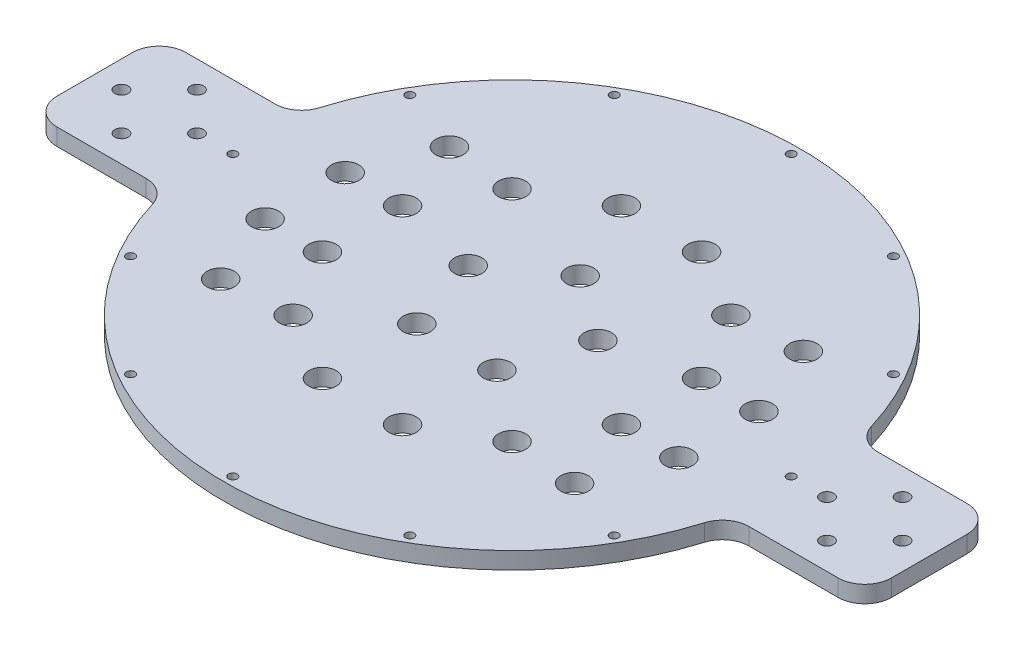
SolidWorks part; units mm, degrees
material "AISI 304"
ref_plane "Front Plane" through (0, 0, 0) normal (0, 0, 1) x (1, 0, 0)
ref_plane "Top Plane" through (0, 0, 0) normal (0, 1, 0) x (1, 0, 0)
ref_plane "Right Plane" through (0, 0, 0) normal (1, 0, 0) x (0, 0, -1)
sketch "Sketch1" plane through (0, 0, 0) normal (0, 1, 0) x (1, 0, 0)
  circle A1 centre (0, 0) radius 107.95
  dimension "D2" = 215.9
extrude "Boss-Extrude1" add sketch "Sketch1" along normal blind 6.35
hole_wizard "M3 Clearance Hole1" positions "Sketch9" profile "Sketch10" hole size "M3" standard "ANSI Metric" end condition through all
sketch "Sketch9" plane through (0, 6.35, 0) normal (0, 1, 0) x (1, 0, 0)
  line L0 (0, 0) -> (0, 104.55) construction
  point P2 (0, 104.55)
  dimension "D1" = 104.55
sketch "Sketch10" plane through (0, 6.35, -104.55) normal (1, 0, 0) x (0, 0, 1)
  line L0 (0, 0) -> (0, 6.35)
  line L1 (0, 6.35) -> (1.6, 6.35)
  line L2 (1.6, 6.35) -> (1.6, 0)
  line L5 (1.6, 0) -> (0, 0)
  line L11 (0, -6.35) -> (0, 107.95) construction
  dimension "Thru Hole Dia." = 3.2
  dimension "Thru Hole Depth" = 6.35
pattern_circular "CirPattern1" count 12 over 360 about axis through (0, 6.35, 0) along (0, -1, 0) of "M3 Clearance Hole1" reverse direction yes
sketch "Sketch2" plane through (0, 0, 0) normal (0, 1, 0) x (1, 0, 0)
  line L0 (-156.2343, 24.1421) -> (-105.2158, 24.1421)
  line L1 (-105.2158, -24.1421) -> (-156.2343, -24.1421)
  line L2 (-156.2343, -24.1421) -> (-156.2343, 24.1421)
  line L3 (-156.2343, 0) -> (0, 0) construction
  line L4 (-146.2343, 0) -> (-132.0921, 14.1421) construction
  line L5 (-132.0921, 14.1421) -> (-117.95, 0) construction
  line L6 (-117.95, 0) -> (-132.0921, -14.1421) construction
  line L7 (-132.0921, -14.1421) -> (-146.2343, 0) construction
  circle A0 centre (0, 0) radius 107.95 construction
  circle A1 centre (0, 0) radius 107.95 construction
  arc A2 (-105.2158, 24.1421) -> (-105.2158, -24.1421) centre (0, 0) ccw
  point P11 (-107.95, 0)
  dimension "D1" = 20
  dimension "D2" = 10
  dimension "D3" = 10
  dimension "D4" = 10
extrude "Boss-Extrude2" add sketch "Sketch2" along normal up to surface (6.35 mm away) up to face at (52.275, 6.35, -88.943)
hole_wizard "#10 Clearance Hole3" positions "Sketch7" profile "Sketch8" hole size "#10" standard "ANSI Inch" end condition through all
sketch "Sketch7" plane through (0, 6.35, 0) normal (0, 1, 0) x (1, 0, 0)
  line L0 (-117.95, 0) -> (-132.0921, -14.1421) construction
  line L1 (-132.0921, -14.1421) -> (-146.2343, 0) construction
  line L2 (-146.2343, 0) -> (-132.0921, 14.1421) construction
  line L3 (-132.0921, 14.1421) -> (-117.95, 0) construction
  line L4 (-117.95, 0) -> (-132.0921, -14.1421) construction
  line L5 (-132.0921, -14.1421) -> (-146.2343, 0) construction
  line L6 (-146.2343, 0) -> (-132.0921, 14.1421) construction
  line L7 (-132.0921, 14.1421) -> (-117.95, 0) construction
  point P0 (-132.0921, -14.1421)
  point P2 (-117.95, 0)
  point P4 (-132.0921, 14.1421)
  point P6 (-146.2343, 0)
sketch "Sketch8" plane through (-132.0921, 6.35, 14.1421) normal (1, 0, 0) x (0, 0, 1)
  line L0 (0, 0) -> (0, 6.35)
  line L1 (0, 6.35) -> (2.4892, 6.35)
  line L2 (2.4892, 6.35) -> (2.4892, 0)
  line L5 (2.4892, 0) -> (0, 0)
  line L11 (0, -6.35) -> (0, 107.95) construction
  dimension "Thru Hole Dia." = 4.9784
  dimension "Thru Hole Depth" = 6.35
fillet "Fillet1" radius 10 4 edges at (-105.2158, 3.175, -24.1421) (-156.2343, 3.175, -24.1421) (-156.2343, 3.175, 24.1421) (-105.2158, 3.175, 24.1421)
mirror "Mirror1" about plane through (0, 0, 0) normal (1, 0, 0) of "#10 Clearance Hole3", "Fillet1", "Boss-Extrude2"
sketch "Sketch11" plane through (0, 6.35, 0) normal (0, 1, 0) x (1, 0, 0)
  line L0 (-88.9, 0) -> (0, 0) construction
  line L1 (0, 0) -> (0, 88.9) construction
  circle A0 centre (0, 0) radius 88.9 construction
  circle A1 centre (-66.2622, 42.8314) radius 5.1
  circle A2 centre (-77.461, 15) radius 5.1
  circle A3 centre (-77.461, -15) radius 5.1
  circle A4 centre (-66.2622, -42.8314) radius 5.1
  circle A9 centre (0, 25.5195) radius 5.1
  circle A10 centre (-24.2705, 7.886) radius 5.1
  circle A11 centre (24.2705, 7.886) radius 5.1
  circle A12 centre (-15, -20.6457) radius 5.1
  circle A13 centre (15, -20.6457) radius 5.1
  circle A14 centre (-55.9808, -15) radius 5.1
  circle A15 centre (-40.9808, -40.9808) radius 5.1
  circle A16 centre (-15, -55.9808) radius 5.1
  circle A17 centre (15, -55.9808) radius 5.1
  circle A18 centre (-55.9808, 15) radius 5.1
  circle A20 centre (55.9808, -15) radius 5.1
  circle A21 centre (40.9808, -40.9808) radius 5.1
  circle A26 centre (0, 0) radius 25.5195 construction
  arc A27 (-64.809, 45) -> (-64.809, -45) centre (0, 0) ccw construction
  circle A28 centre (66.2622, -42.8314) radius 5.1
  circle A29 centre (77.461, -15) radius 5.1
  circle A30 centre (77.461, 15) radius 5.1
  circle A31 centre (66.2622, 42.8314) radius 5.1
  circle A32 centre (0, 0) radius 57.9555 construction
  circle A33 centre (55.9808, 15) radius 5.1
  circle A34 centre (40.9808, 40.9808) radius 5.1
  circle A35 centre (15, 55.9808) radius 5.1
  circle A36 centre (-15, 55.9808) radius 5.1
  circle A37 centre (-40.9808, 40.9808) radius 5.1
  dimension "D1" = 177.8
  dimension "D2" = 10.2
  dimension "D3" = 30
  dimension "D8" = 10
  dimension "D9" = 90
  dimension "D11" = 30
  dimension "D4" = 30
  dimension "D5" = 30
  dimension "D6" = 30
  dimension "D7" = 30
  dimension "D10" = 30
  dimension "D12" = 30
  dimension "D13" = 30
  dimension "D14" = 30
  dimension "D15" = 30
  dimension "D16" = 30
  dimension "D17" = 30
  dimension "D18" = 30
  dimension "D19" = 30
extrude "Cut-Extrude1" cut sketch "Sketch11" against normal up to next (6.35 mm away)
